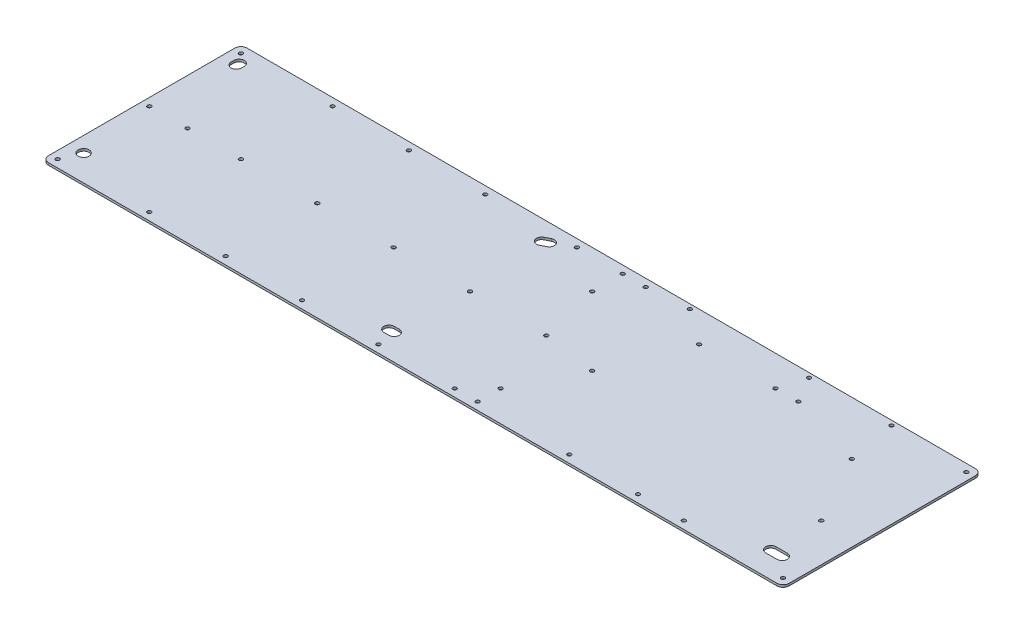
SolidWorks part; units mm, degrees
ref_plane "Front Plane" through (0, 0, 0) normal (0, 0, 1) x (1, 0, 0)
ref_plane "Top Plane" through (0, 0, 0) normal (0, 1, 0) x (1, 0, 0)
ref_plane "Right Plane" through (0, 0, 0) normal (1, 0, 0) x (0, 0, -1)
sketch "Sketch1" plane through (0, 0, 0) normal (0, 1, 0) x (1, 0, 0)
  line L41 (10.0785, 118.7126) -> (10.0785, 116.8884) construction
  line L144 (0, 130) -> (485, 130)
  line L147 (0, 130) -> (0, 0)
  line L150 (0, 0) -> (485, 0)
  line L175 (485, 130) -> (485, 0)
  line L176 (13.4866, 118.7126) -> (13.4866, 116.8884)
  line L177 (6.6704, 118.7126) -> (6.6704, 116.8884)
  line L178 (213.3033, 118.6001) -> (209.9889, 116.9437) construction
  line L179 (214.8114, 115.5824) -> (211.4969, 113.926)
  line L180 (211.7953, 121.6178) -> (208.4808, 119.9614)
  line L181 (209.9889, 17) -> (213.3033, 17) construction
  line L182 (209.9889, 20.409) -> (213.3033, 20.409)
  line L183 (209.9889, 13.591) -> (213.3033, 13.591)
  line L184 (467.3766, 17) -> (460, 17) construction
  line L185 (467.3766, 13.5587) -> (460, 13.5587)
  line L186 (467.3766, 20.4413) -> (460, 20.4413)
  circle A35 centre (5, 125) radius 1.25
  circle A36 centre (65, 125) radius 1.25
  circle A37 centre (5, 65) radius 1.25
  circle A38 centre (30, 65) radius 1.25
  circle A39 centre (65, 65) radius 1.25
  circle A40 centre (115, 125) radius 1.25
  circle A41 centre (115, 65) radius 1.25
  circle A42 centre (5, 5) radius 1.25
  circle A43 centre (65, 5) radius 1.25
  circle A44 centre (115, 5) radius 1.25
  circle A45 centre (165, 5) radius 1.25
  circle A46 centre (215, 5) radius 1.25
  circle A47 centre (265, 5) radius 1.25
  circle A48 centre (280, 5) radius 1.25
  circle A49 centre (280, 20) radius 1.25
  circle A50 centre (415, 5) radius 1.25
  circle A51 centre (385, 5) radius 1.25
  circle A52 centre (339.9969, 5) radius 1.25
  circle A53 centre (480, 5) radius 1.25
  circle A54 centre (460, 50) radius 1.25
  circle A55 centre (435, 95) radius 1.25
  circle A56 centre (369.9978, 110.0294) radius 1.25
  circle A57 centre (385, 110.0294) radius 1.25
  circle A58 centre (480, 125) radius 1.25
  circle A59 centre (429, 127) radius 1.25
  circle A60 centre (374.95, 127) radius 1.25
  circle A61 centre (300, 60) radius 1.25
  circle A62 centre (265, 65) radius 1.25
  circle A63 centre (255, 105) radius 1.25
  circle A64 centre (320, 110) radius 1.25
  circle A65 centre (297, 127) radius 1.25
  circle A66 centre (270, 125) radius 1.25
  circle A67 centre (255, 125) radius 1.25
  circle A68 centre (215, 65) radius 1.25
  circle A69 centre (165, 65) radius 1.25
  circle A70 centre (165, 125) radius 1.25
  circle A71 centre (215, 125) radius 1.25 construction
  arc A72 (13.4866, 118.7126) -> (6.6704, 118.7126) centre (10.0785, 118.7126) ccw
  arc A73 (6.6704, 116.8884) -> (13.4866, 116.8884) centre (10.0785, 116.8884) ccw
  circle A74 centre (10, 17) radius 3.5772
  arc A75 (214.8114, 115.5824) -> (211.7953, 121.6178) centre (213.3033, 118.6001) ccw
  arc A76 (208.4808, 119.9614) -> (211.4969, 113.926) centre (209.9889, 116.9437) ccw
  arc A77 (209.9889, 20.409) -> (209.9889, 13.591) centre (209.9889, 17) ccw
  arc A78 (213.3033, 13.591) -> (213.3033, 20.409) centre (213.3033, 17) ccw
  arc A79 (467.3766, 13.5587) -> (467.3766, 20.4413) centre (467.3766, 17) ccw
  arc A80 (460, 20.4413) -> (460, 13.5587) centre (460, 17) ccw
  circle A81 centre (225, 125) radius 1.25
  point P80 (10.0785, 117.8005)
  point P87 (211.6461, 117.7719)
  point P94 (211.6461, 17)
  point P101 (463.6883, 17)
  dimension "D1" = 2.5
  dimension "D2" = 10
extrude "Boss-Extrude1" add sketch "Sketch1" against normal blind 1.5 from offset 4 contours L147 L150 L175 region at (242.5711, 0, -65.0397) offset against normal yes
fillet "Fillet1" radius 4 4 edges at (485, -4.75, 0) (485, -4.75, -130) (0, -4.75, 0) (0, -4.75, -130)
